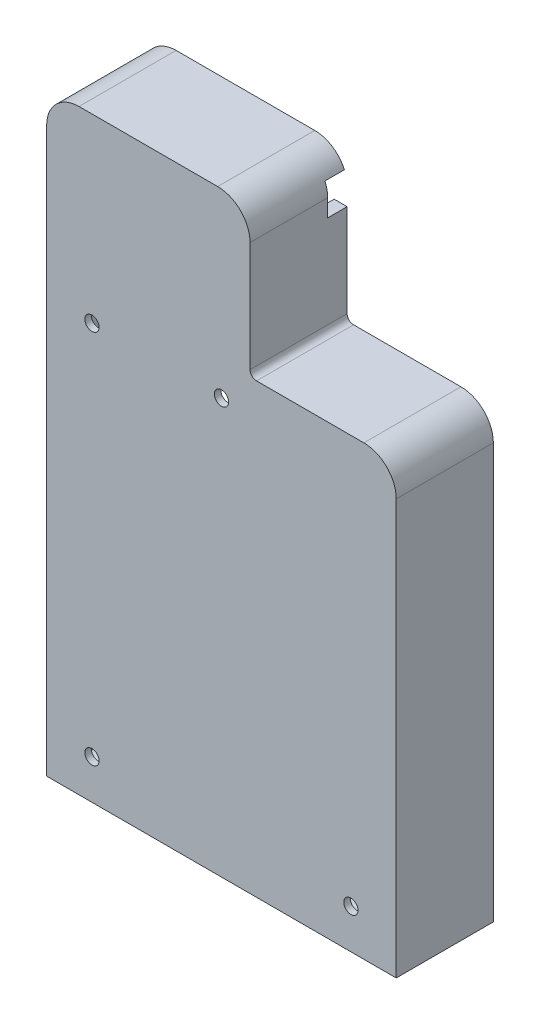
SolidWorks part; units mm, degrees
other "Markup1"
sketch "Sketch13" plane through (0.4487, 1125.5894, 1303.4729) normal (-0.633, 0.4523, -0.6282) x (-0.2198, -0.8831, -0.4145)
ref_plane "Front Plane" through (0, 0, 0) normal (0, 0, 1) x (1, 0, 0)
ref_plane "Top Plane" through (0, 0, 0) normal (0, 1, 0) x (1, 0, 0)
ref_plane "Right Plane" through (0, 0, 0) normal (1, 0, 0) x (0, 0, -1)
sketch "Sketch3" plane through (0, 0, 1303.4729) normal (0, 0, 1) x (1, 0, 0)
  line L0 (787.6501, 933.5894) -> (787.6501, 1120.5894) construction
  line L1 (787.6501, 1035.4965) -> (787.6501, 1120.5894)
  line L2 (837.6501, 1097.5894) -> (837.6501, 933.5894) construction
  line L3 (818.0661, 1100.5894) -> (834.6501, 1100.5894) construction
  line L4 (815.0661, 1120.5894) -> (815.0661, 1103.5894) construction
  line L5 (790.6501, 1123.5894) -> (812.0661, 1123.5894) construction
  line L6 (837.6501, 1097.5894) -> (837.6501, 1035.4965)
  line L7 (818.0661, 1100.5894) -> (834.6501, 1100.5894)
  line L8 (815.0661, 1120.5894) -> (815.0661, 1103.5894)
  line L9 (790.6501, 1123.5894) -> (812.0661, 1123.5894)
  line L10 (787.6501, 1035.4965) -> (837.6501, 1035.4965) construction
  line L11 (787.6501, 1035.4965) -> (837.6501, 1035.4965)
  line L12 (839.6501, 1097.5898) -> (839.6501, 1033.4965)
  line L13 (785.6501, 1033.4965) -> (839.6501, 1033.4965)
  line L14 (785.6501, 1033.4965) -> (785.6501, 1120.5898)
  line L15 (790.6497, 1125.5894) -> (812.0665, 1125.5894)
  line L16 (817.0661, 1120.5898) -> (817.0661, 1103.5898)
  line L17 (818.0665, 1102.5894) -> (834.6505, 1102.5894)
  arc A0 (837.6501, 1097.5894) -> (834.6501, 1100.5894) centre (834.649, 1097.5883) ccw construction
  arc A1 (815.0661, 1103.5894) -> (818.0661, 1100.5894) centre (818.0672, 1103.5905) ccw construction
  arc A2 (815.0661, 1120.5894) -> (812.0661, 1123.5894) centre (812.065, 1120.5883) ccw construction
  arc A3 (790.6501, 1123.5894) -> (787.6501, 1120.5894) centre (790.6512, 1120.5883) ccw construction
  arc A4 (837.6501, 1097.5894) -> (834.6501, 1100.5894) centre (834.649, 1097.5883) ccw
  arc A5 (815.0661, 1103.5894) -> (818.0661, 1100.5894) centre (818.0672, 1103.5905) ccw
  arc A6 (815.0661, 1120.5894) -> (812.0661, 1123.5894) centre (812.065, 1120.5883) ccw
  arc A7 (790.6501, 1123.5894) -> (787.6501, 1120.5894) centre (790.6512, 1120.5883) ccw
  arc A8 (790.6497, 1125.5894) -> (785.6501, 1120.5898) centre (790.6512, 1120.5883) ccw
  arc A9 (817.0661, 1120.5898) -> (812.0665, 1125.5894) centre (812.065, 1120.5883) ccw
  arc A10 (817.0661, 1103.5898) -> (818.0665, 1102.5894) centre (818.0672, 1103.5905) ccw
  arc A11 (839.6501, 1097.5898) -> (834.6505, 1102.5894) centre (834.649, 1097.5883) ccw
  dimension "D1" = 2
sketch "Sketch6" plane through (0, 0, 1303.4729) normal (0, 0, 1) x (1, 0, 0)
  line L0 (787.6501, 1035.4965) -> (837.6501, 1035.4965) construction
  line L1 (837.6501, 1097.5894) -> (837.6501, 1035.4965) construction
  line L2 (818.0661, 1100.5894) -> (834.6501, 1100.5894) construction
  line L3 (815.0661, 1120.5894) -> (815.0661, 1103.5894) construction
  line L4 (790.6501, 1123.5894) -> (812.0661, 1123.5894) construction
  line L5 (787.6501, 1035.4965) -> (787.6501, 1120.5894) construction
  line L6 (787.6501, 1035.4965) -> (837.6501, 1035.4965)
  line L7 (837.6501, 1097.5894) -> (837.6501, 1035.4965)
  line L8 (818.0661, 1100.5894) -> (834.6501, 1100.5894)
  line L9 (815.0661, 1120.5894) -> (815.0661, 1103.5894)
  line L10 (790.6501, 1123.5894) -> (812.0661, 1123.5894)
  line L11 (787.6501, 1035.4965) -> (787.6501, 1120.5894)
  arc A0 (837.6501, 1097.5894) -> (834.6501, 1100.5894) centre (834.649, 1097.5883) ccw construction
  arc A1 (815.0661, 1103.5894) -> (818.0661, 1100.5894) centre (818.0672, 1103.5905) ccw construction
  arc A2 (815.0661, 1120.5894) -> (812.0661, 1123.5894) centre (812.065, 1120.5883) ccw construction
  arc A3 (790.6501, 1123.5894) -> (787.6501, 1120.5894) centre (790.6512, 1120.5883) ccw construction
  arc A4 (837.6501, 1097.5894) -> (834.6501, 1100.5894) centre (834.649, 1097.5883) ccw
  arc A5 (815.0661, 1103.5894) -> (818.0661, 1100.5894) centre (818.0672, 1103.5905) ccw
  arc A6 (815.0661, 1120.5894) -> (812.0661, 1123.5894) centre (812.065, 1120.5883) ccw
  arc A7 (790.6501, 1123.5894) -> (787.6501, 1120.5894) centre (790.6512, 1120.5883) ccw
extrude "Boss-Extrude1" add sketch "Sketch3" along normal blind 15
extrude "Boss-Extrude2" add sketch "Sketch6" along normal blind 15
extrude "Cut-Extrude1" cut sketch "Sketch6<2>" along normal blind 14
sketch "Sketch6<2>" plane through (0, 0, 1303.4729) normal (0, 0, 1) x (1, 0, 0) same geometry as "Sketch6"
sketch "Sketch8" plane through (0, 0, 1303.4729) normal (0, 0, 1) x (1, 0, 0)
  line L10 (791.5267, 1122.6166) -> (784.8275, 1122.6166)
  line L11 (791.5267, 1122.6166) -> (791.5267, 1117.8952)
  line L12 (791.5267, 1117.8952) -> (784.8275, 1117.8952)
  line L13 (784.8275, 1122.6166) -> (784.8275, 1117.8952)
  line L14 (809.8444, 1122.6166) -> (818.0733, 1122.6166)
  line L15 (809.8444, 1122.6166) -> (809.8444, 1117.8952)
  line L16 (809.8444, 1117.8952) -> (818.0733, 1117.8952)
  line L17 (818.0733, 1122.6166) -> (818.0733, 1117.8952)
extrude "Cut-Extrude7" cut sketch "Sketch8" along normal blind 3
sketch "Sketch10" plane through (0, 0, 1303.4729) normal (0, 0, 1) x (1, 0, 0)
  circle A0 centre (832.6501, 1039.5894) radius 1.1 construction
  circle A1 centre (792.6501, 1039.5894) radius 1.1 construction
  circle A2 centre (792.6501, 1097.5894) radius 1.1 construction
  circle A3 centre (812.6501, 1097.5894) radius 1.1 construction
  circle A4 centre (832.6501, 1039.5894) radius 1.1
  circle A5 centre (792.6501, 1039.5894) radius 1.1
  circle A6 centre (792.6501, 1097.5894) radius 1.1
  circle A7 centre (812.6501, 1097.5894) radius 1.1
  point P12 (0, 0)
extrude "Cut-Extrude9" cut sketch "Sketch10" along normal up to surface (15 mm away) up to face at (814.0994, 1096.8608, 1318.4729)
